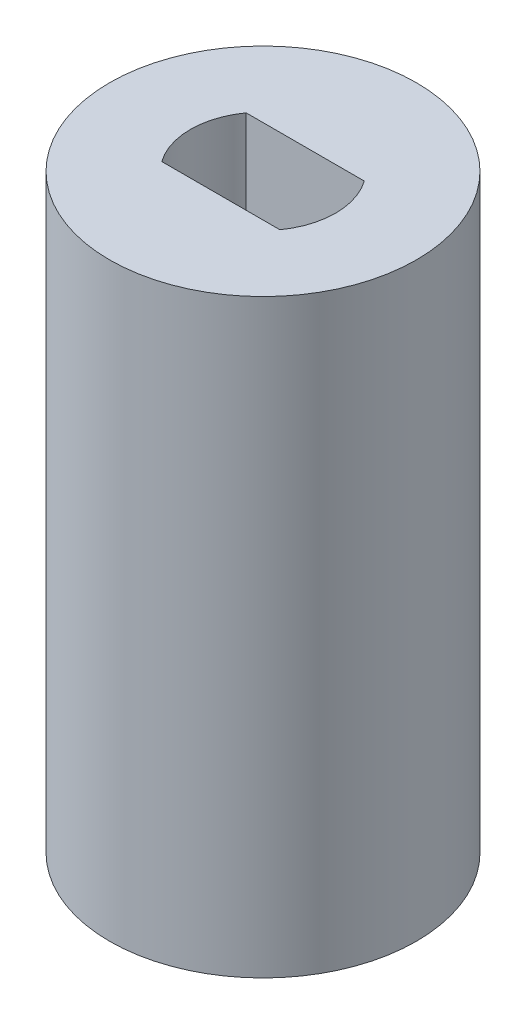
SolidWorks part; units mm, degrees
material "Custom Plastic"
ref_plane "Front Plane" through (0, 0, 0) normal (0, 0, 1) x (1, 0, 0)
ref_plane "Top Plane" through (0, 0, 0) normal (0, 1, 0) x (1, 0, 0)
ref_plane "Right Plane" through (0, 0, 0) normal (1, 0, 0) x (0, 0, -1)
sketch "Sketch1" plane through (0, 0, 0) normal (0, 0, 1) x (1, 0, 0)
  line L0 (0, 0) -> (0, 12.2143) construction
  line L1 (-1.2, 0) -> (-1.2, 20)
  line L2 (-1.2, 20) -> (-5.2, 20)
  line L3 (-5.2, 20) -> (-5.2, 0)
  line L4 (-5.2, 0) -> (-1.2, 0)
  dimension "D1" = 2.4
  dimension "D2" = 4
  dimension "D3" = 20
revolve "Revolve1" add sketch "Sketch1" angle 360 about L0
sketch "Sketch3" plane through (0, 20, 0) normal (0, 1, 0) x (1, 0, 0)
  line L1 (-2.0017, 1.43) -> (2.0017, 1.43)
  line L2 (-2.0017, 1.43) -> (-2.0017, -1.43) construction
  line L3 (-2.0017, -1.43) -> (2.0017, -1.43)
  line L4 (2.0017, 1.43) -> (2.0017, -1.43) construction
  arc A0 (-2.0017, 1.43) -> (-2.0017, -1.43) centre (0, 0) ccw
  arc A1 (2.0017, 1.43) -> (-2.0017, 1.43) centre (0, 0) ccw construction
  arc A2 (2.0017, -1.43) -> (2.0017, 1.43) centre (0, 0) ccw
  arc A3 (-2.0017, -1.43) -> (2.0017, -1.43) centre (0, 0) ccw construction
  dimension "D2" = 4.92
  dimension "D1" = 2.86
extrude "Cut-Extrude1" cut sketch "Sketch3" against normal blind 8
